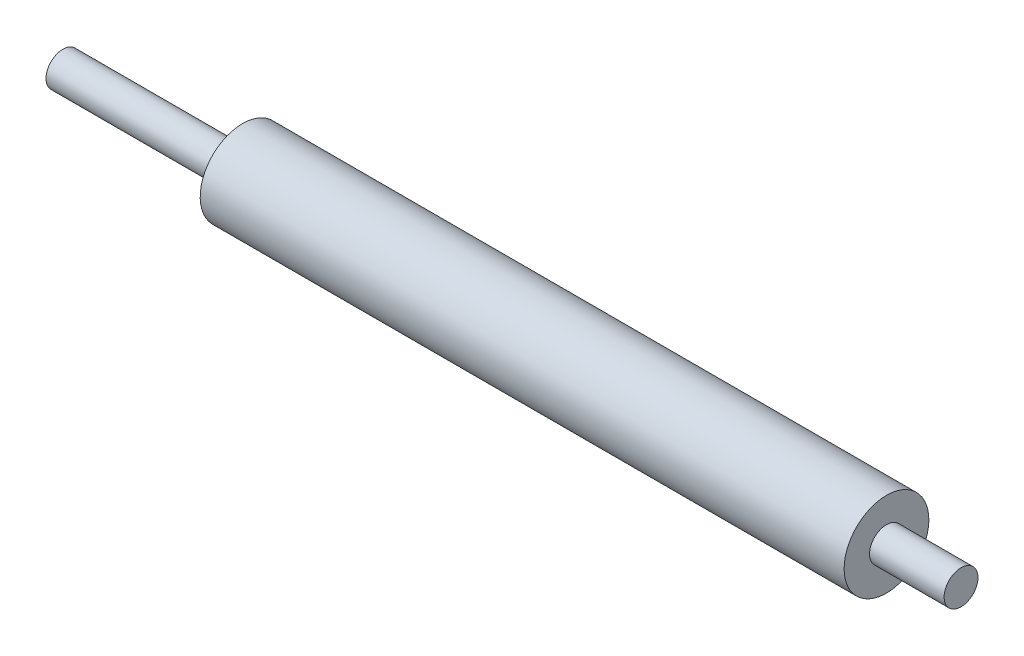
SolidWorks part; units mm, degrees
ref_plane "Front Plane" through (0, 0, 0) normal (0, 0, 1) x (1, 0, 0)
ref_plane "Top Plane" through (0, 0, 0) normal (0, 1, 0) x (1, 0, 0)
ref_plane "Right Plane" through (0, 0, 0) normal (1, 0, 0) x (0, 0, -1)
sketch "Sketch2" plane through (0, 0, 0) normal (0, 0, 1) x (1, 0, 0)
  line L0 (0, 0) -> (0, 5)
  line L1 (0, 5) -> (53, 5)
  line L2 (53, 5) -> (53, 12.5)
  line L3 (53, 12.5) -> (243, 12.5)
  line L4 (243, 12.5) -> (243, 5)
  line L5 (243, 5) -> (265, 5)
  line L6 (265, 5) -> (265, 0)
  line L7 (265, 0) -> (0, 0)
  dimension "D1" = 5
  dimension "D2" = 53
  dimension "D3" = 22
  dimension "D4" = 190
  dimension "D5" = 12.5
revolve "Revolve1" add sketch "Sketch2" angle 360 about L7
